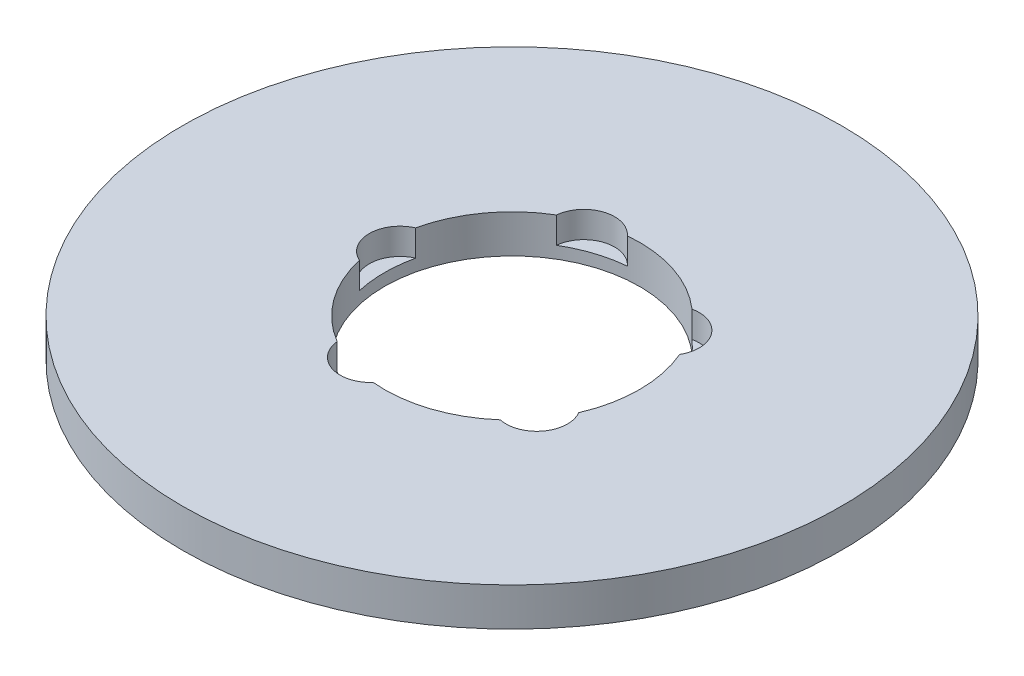
SolidWorks part; units mm, degrees
ref_plane "Front Plane" through (0, 0, 0) normal (0, 0, 1) x (1, 0, 0)
ref_plane "Top Plane" through (0, 0, 0) normal (0, 1, 0) x (1, 0, 0)
ref_plane "Right Plane" through (0, 0, 0) normal (1, 0, 0) x (0, 0, -1)
sketch "Sketch1" plane through (0, 0, 0) normal (0, 1, 0) x (1, 0, 0)
  circle A0 centre (0, 0) radius 77.5
  dimension "FLANGE_OD" = 155
extrude "Boss-Extrude1" add sketch "Sketch1" along normal blind 9
sketch "Sketch2" plane through (0, 0, 0) normal (0, 1, 0) x (1, 0, 0)
  circle A0 centre (0, 0) radius 30
  dimension "BORE_D" = 60
extrude "Cut-Extrude1" cut sketch "Sketch2" along normal through all
sketch "Sketch3" plane through (0, 9, 0) normal (0, 1, 0) x (1, 0, 0)
  circle A0 centre (0, 0) radius 26.34 construction
  circle A1 centre (-26.34, 0) radius 7.2271
  dimension "BOLT_D" = 14.4542
  dimension "BOLT_PCD" = 52.68
extrude "Cut-Extrude2" cut sketch "Sketch3" against normal blind 6.1748
pattern_circular "CirPattern1" count 5 over 360 about axis through (0, 0, 0) along (0, 1, 0) of "Cut-Extrude2"
